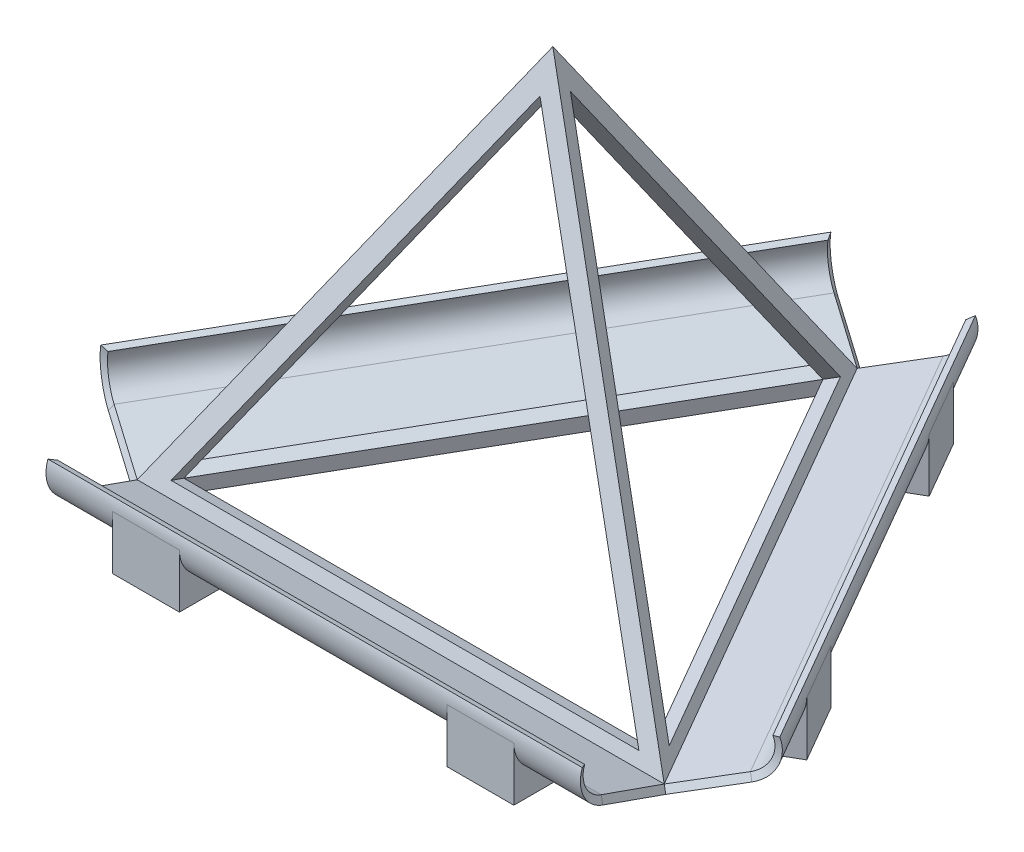
SolidWorks part; units mm, degrees
ref_plane "Front Plane" through (0, 0, 0) normal (0, 0, 1) x (1, 0, 0)
ref_plane "Top Plane" through (0, 0, 0) normal (0, 1, 0) x (1, 0, 0)
ref_plane "Right Plane" through (0, 0, 0) normal (1, 0, 0) x (0, 0, -1)
sketch "Sketch1" plane through (0, 0, 0) normal (0, 1, 0) x (1, 0, 0)
  line L0 (-50.8, -29.3294) -> (0, 58.6588)
  line L1 (0, 58.6588) -> (50.8, -29.3294)
  line L2 (50.8, -29.3294) -> (-50.8, -29.3294)
  line L3 (-50.8, -29.3294) -> (0, 0) construction
  line L4 (0, 0) -> (0, -29.3294) construction
  dimension "D1" = 101.6
extrude "Boss-Extrude1" add sketch "Sketch1" along normal blind 82.9561 contours L0 L1 L2
chamfer "Chamfer1" distance 29.3294 distance2 83.058 3 edges at (-25.4, 82.9561, -14.6647) (0, 82.9561, 29.3294) (25.4, 82.9561, -14.6647) first distance on face at (0, 82.9561, 0)
sketch "Sketch2" plane through (0, 0, 0) normal (0, 1, 0) x (1, 0, 0)
  line L0 (-44.45, -25.6632) -> (0, 51.3264)
  line L1 (0, 51.3264) -> (44.45, -25.6632)
  line L2 (44.45, -25.6632) -> (-44.45, -25.6632)
  line L3 (0, 0) -> (0, 51.3264) construction
  line L4 (-22.225, 12.8316) -> (0, 0) construction
  dimension "D1" = 88.9
extrude "Boss-Extrude3" add sketch "Sketch2" along normal blind 72.5865 from offset 2.5924 separate body
chamfer "Chamfer6" distance 72.644 distance2 25.6632 3 edges at (22.225, 75.1789, -12.8316) (-22.225, 75.1789, -12.8316) (0, 75.1789, 25.6632) first distance on face at (22.225, 38.8856, -12.8316) first distance on face at (-22.225, 38.8856, -12.8316) first distance on face at (0, 38.8856, 25.6632)
sketch "Sketch19" plane through (0, 8.3415, 23.6119) normal (0, 0.3331, 0.9429) x (1, 0, 0)
  line L0 (0, 70.8856) -> (-44.4148, -6.0973)
  line L1 (-44.4148, -6.0973) -> (44.4148, -6.0973)
  line L2 (44.4148, -6.0973) -> (0, 70.8856)
extrude "Boss-Extrude19" add sketch "Sketch19" along normal blind 25.4
sketch "Sketch20" plane through (-20.4485, 8.3415, -11.806) normal (-0.8166, 0.3331, -0.4714) x (-0.4365, 0.1781, 0.8819)
  line L0 (13.387, 69.61) -> (42.4641, -14.3755)
  line L1 (42.4641, -14.3755) -> (-44.7671, 2.4003)
  line L2 (-44.7671, 2.4003) -> (13.387, 69.61)
extrude "Boss-Extrude20" add sketch "Sketch20" along normal blind 25.4
sketch "Sketch21" plane through (20.4485, 8.3415, -11.806) normal (0.8166, 0.3331, -0.4714) x (-0.4365, -0.1781, -0.8819)
  line L0 (-13.387, 69.61) -> (-42.4641, -14.3755)
  line L1 (-42.4641, -14.3755) -> (44.7671, 2.4003)
  line L2 (44.7671, 2.4003) -> (-13.387, 69.61)
extrude "Boss-Extrude21" add sketch "Sketch21" along normal blind 25.4
sketch "Sketch22" plane through (0, 2.5924, 0) normal (0, -1, 0) x (1, 0, 0)
  line L0 (44.4148, 25.6429) -> (-44.4148, 25.6429)
  line L1 (-44.4148, 25.6429) -> (0, -51.2858)
  line L2 (0, -51.2858) -> (44.4148, 25.6429)
extrude "Boss-Extrude23" add sketch "Sketch22" along normal blind 25.4
combine bodies "Combine3" operation type subtract main body 101 bodies to subtract 125
sketch "Sketch24" plane through (0, 9.1972, 26.0457) normal (0, 0.333, 0.9429) x (1, 0, 0)
  line L0 (-50.7376, -9.7538) -> (50.7376, -9.7538)
  line L1 (50.7376, -9.7538) -> (50.034, -8.5337)
  line L2 (0, 78.2224) -> (50.7376, -9.7538) construction
  line L3 (50.034, -8.5337) -> (-50.034, -8.5337)
  line L4 (-50.7376, -9.7538) -> (0, 78.2224) construction
  line L5 (-50.034, -8.5337) -> (-50.7376, -9.7538)
  line L6 (44.4148, -6.0935) -> (-44.4148, -6.0935) construction
  dimension "D1" = 3.6603
  dimension "D2" = 1.2201
sketch "Sketch25" plane through (0, 0, 0) normal (1, 0, 0) x (0, 0, -1)
  line L0 (-29.2934, 0) -> (-41.2687, 4.2287)
  arc A0 (-41.2687, 4.2287) -> (-45.142, 12.3307) centre (-39.1543, 10.2164) cw
  dimension "D2" = 6.35
  dimension "D1" = 12.7
sweep "Sweep2" add profiles "Sketch24" path "Sketch25"
sketch "Sketch26" plane through (0, 0, 0) normal (1, 0, 0) x (0, 0, -1)
  line L0 (-45.5043, 10.2164) -> (-45.5043, 0)
  line L1 (-45.5043, 0) -> (-29.2934, 0)
  line L2 (-29.2934, 0) -> (-41.2687, 4.2287)
  arc A1 (-41.2687, 4.2287) -> (-45.5043, 10.2164) centre (-39.1543, 10.2164) cw
extrude "Boss-Extrude26" add sketch "Sketch26" along normal blind 12.7 from offset 25.4 contours L0 L1 L2 A1
extrude "Boss-Extrude27" add sketch "Sketch26<7>" against normal blind 12.7 from offset 25.4 offset against normal yes
sketch "Sketch26<7>" plane through (0, 0, 0) normal (1, 0, 0) x (0, 0, -1) same geometry as "Sketch26"
sketch "Sketch27" plane through (0, 0, 0) normal (0, -1, 0) x (-1, 0, 0)
  line L0 (50.7376, -29.2934) -> (-25.3688, 14.6467) construction
  line L1 (0, 58.5868) -> (-50.7376, -29.2934) construction
ref_plane "Plane1" through (0, 0, 0) normal (0.5, 0, 0.866) x (0.866, 0, -0.5)
sketch "Sketch28" plane through (0, 0, 0) normal (0, -1, 0) x (1, 0, 0)
  line L0 (50.7376, 29.2934) -> (-25.3688, -14.6467) construction
  line L1 (-50.7376, 29.2934) -> (0, -58.5868) construction
ref_plane "Plane2" through (0, 0, 0) normal (-0.5, 0, 0.866) x (0.866, 0, 0.5)
mirror "Mirror1" about plane through (0, 0, 0) normal (-0.5, 0, 0.866) of "Boss-Extrude26", "Boss-Extrude27", "Sweep2"
mirror "Mirror2" about plane through (0, 0, 0) normal (0.5, 0, 0.866) of "Mirror1"
equation "\"OuterTriHeight\"= 1 / 3 * ( sqr ( 6 ) * 4 )"
equation "\"InnerTriHeight\"= 1 / 3 * ( sqr ( 6 ) * 3.5 )"
equation "\"D1@Boss-Extrude1\"=\"OuterTriHeight\""
equation "\"D1@Boss-Extrude3\"=\"InnerTriHeight\""
equation "\"D19@Boss-Extrude3\"=(\"OuterTriHeight\"-\"InnerTriHeight\")/4"
equation "\"D2@Sketch24\"=\"D1@Sketch24\"/3"
